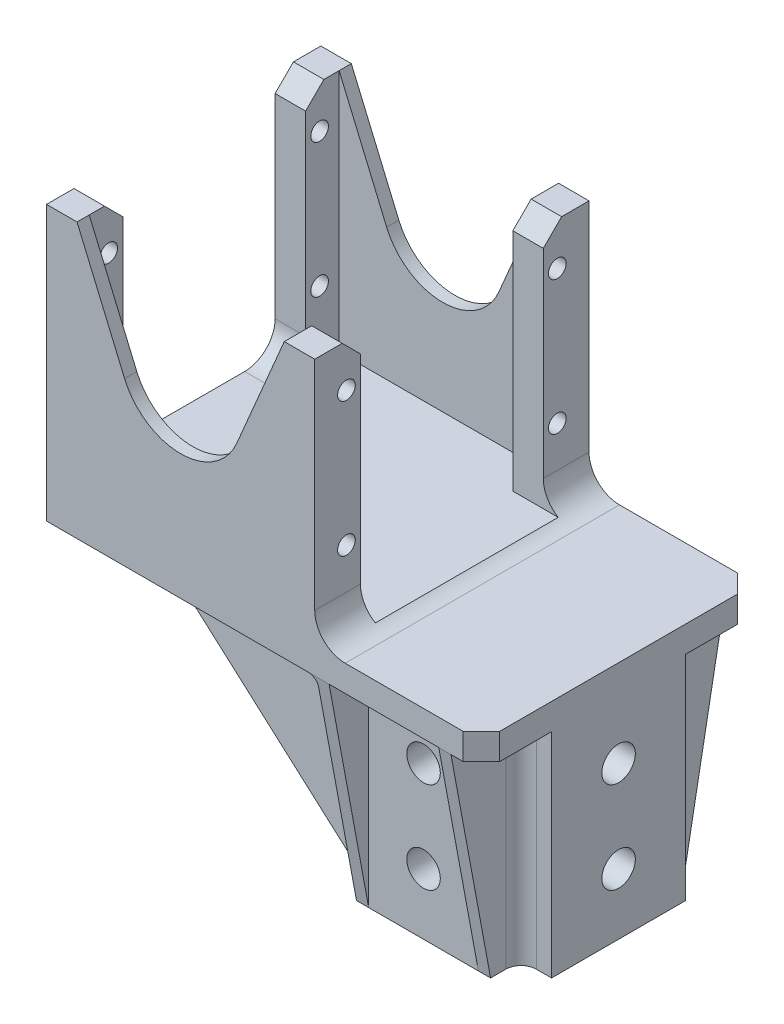
SolidWorks part; units mm, degrees
material "PLA"
ref_plane "Front Plane" through (0, 0, 0) normal (0, 0, 1) x (1, 0, 0)
ref_plane "Top Plane" through (0, 0, 0) normal (0, 1, 0) x (1, 0, 0)
ref_plane "Right Plane" through (0, 0, 0) normal (1, 0, 0) x (0, 0, -1)
sketch "Sketch2" plane through (0, 0, 0) normal (0, 0, 1) x (1, 0, 0)
  line L0 (12.8375, 22.5) -> (17.8375, 22.5) construction
  line L1 (-53.5125, 22.5) -> (17.8375, 22.5) construction
  line L2 (-17.8375, 22.5) -> (-17.8375, -22.5) construction
  line L3 (-53.5125, -22.5) -> (17.8375, -22.5)
  line L4 (17.8375, 22.5) -> (17.8375, -22.5) construction
  line L5 (-17.8375, 22.5) -> (17.8375, -22.5) construction
  line L6 (-17.8375, -22.5) -> (17.8375, 22.5) construction
  line L7 (-48.5125, 22.5) -> (12.8375, 22.5) construction
  line L8 (-17.8375, 22.5) -> (-17.8375, -17.5) construction
  line L9 (-48.5125, -17.5) -> (12.8375, -17.5) construction
  line L10 (12.8375, 22.5) -> (12.8375, -17.5) construction
  line L11 (-17.8375, 22.5) -> (12.8375, -17.5) construction
  line L12 (-17.8375, -17.5) -> (12.8375, 22.5) construction
  line L14 (-17.8375, -17.5) -> (-48.5125, 22.5) construction
  line L15 (-17.8375, 22.5) -> (-48.5125, -17.5) construction
  line L16 (-17.8375, -22.5) -> (-53.5125, 22.5) construction
  line L17 (-17.8375, 22.5) -> (-53.5125, -22.5) construction
  line L18 (-48.5125, 22.5) -> (-48.5125, -17.5)
  line L19 (-53.5125, 22.5) -> (-53.5125, -22.5)
  line L20 (-48.5125, 22.5) -> (-53.5125, 22.5)
  line L22 (-9.5125, -17.5) -> (-9.5125, 22.5)
  line L23 (-9.5125, 22.5) -> (-14.5125, 22.5)
  line L24 (-14.5125, 22.5) -> (-14.5125, -17.5)
  line L26 (17.8375, -17.5) -> (17.8375, -22.5)
  line L27 (-48.5125, -17.5) -> (-14.5125, -17.5)
  line L28 (-9.5125, -17.5) -> (17.8375, -17.5)
  point P4 (0, 0)
  point P8 (-2.5, 2.5)
  point P14 (-33.175, 2.5)
  point P15 (-35.675, 0)
  dimension "D1" = 5
  dimension "D2" = 40
  dimension "D3" = 27.35
  dimension "D4" = 5
  dimension "D5" = 34
  dimension "D6" = 5
extrude "Boss-Extrude1" add sketch "Sketch2" along normal blind 45
sketch "Sketch3" plane through (-53.5125, 0, 0) normal (1, 0, 0) x (0, 0, -1)
  line L0 (-5.2, 22.5) -> (-5.2, -22.5) construction
  line L2 (-39.8, 22.5) -> (-39.8, -22.5) construction
  line L4 (-37.5, 22.5) -> (-7.5, 22.5)
  line L5 (-37.5, 22.5) -> (-37.5, -17.5)
  line L6 (-37.5, -17.5) -> (-7.5, -17.5)
  line L7 (-7.5, 22.5) -> (-7.5, -17.5)
  line L8 (-37.5, 22.5) -> (-7.5, -17.5) construction
  line L9 (-37.5, -17.5) -> (-7.5, 22.5) construction
  line L10 (-45, 22.5) -> (0, 22.5) construction
  line L11 (-39.8, 15.5) -> (-5.2, 15.5) construction
  line L12 (-39.8, -6.5) -> (-5.2, -6.5) construction
  line L13 (-45, -22.5) -> (0, -22.5) construction
  circle A2 centre (-5.2, 15.5) radius 1.25 construction
  circle A3 centre (-5.2, -6.5) radius 1.25 construction
  circle A4 centre (-39.8, 15.5) radius 1.25 construction
  circle A5 centre (-39.8, -6.5) radius 1.25 construction
  point P10 (-22.5, 2.5)
  dimension "D4" = 2.3
  dimension "D7" = 2.5
  dimension "D5" = 2.5
  dimension "D6" = 2.5
  dimension "D9" = 2.5
  dimension "D8" = 22
  dimension "D1" = 30
  dimension "D2" = 5
  dimension "D3" = 2.3
  dimension "D10" = 11
extrude "Cut-Extrude1" cut sketch "Sketch3" along normal through all
sketch "Sketch4" plane through (0, -22.5, 0) normal (0, -1, 0) x (1, 0, 0)
  line L0 (-53.5125, 22.5) -> (17.8375, 22.5) construction
  line L1 (17.8375, 45) -> (17.8375, 0) construction
  line L3 (-53.5125, 45) -> (-53.5125, 0) construction
  line L10 (-8.4125, 32.75) -> (12.0875, 32.75)
  line L11 (-8.4125, 32.75) -> (-8.4125, 12.25)
  line L12 (-8.4125, 12.25) -> (12.0875, 12.25)
  line L13 (12.0875, 32.75) -> (12.0875, 12.25)
  line L14 (-8.4125, 32.75) -> (12.0875, 12.25) construction
  line L15 (-8.4125, 12.25) -> (12.0875, 32.75) construction
  line L16 (-14.1625, 38.5) -> (17.8375, 38.5)
  line L17 (-14.1625, 38.5) -> (-14.1625, 6.5)
  line L18 (-14.1625, 6.5) -> (17.8375, 6.5)
  line L19 (17.8375, 38.5) -> (17.8375, 6.5)
  line L20 (-14.1625, 38.5) -> (17.8375, 6.5) construction
  line L21 (-14.1625, 6.5) -> (17.8375, 38.5) construction
  circle A0 centre (1.8375, 22.5) radius 2.5
  point P18 (1.8375, 22.5)
  point P23 (1.8375, 22.5)
  dimension "D1" = 5
  dimension "D2" = 20.5
  dimension "D3" = 20.5
  dimension "D4" = 32
extrude "Boss-Extrude2" add sketch "Sketch4" along normal blind 35 contours L19 L16 L17 L18 L10 L13 L12 L11 region at (1.8375, -22.5, 38.0475)
sketch "Sketch5" plane through (0, 0, 38.5) normal (0, 0, 1) x (1, 0, 0)
  line L0 (1.8375, -22.5) -> (1.8375, -57.5) construction
  line L3 (-14.1625, -22.5) -> (17.8375, -22.5) construction
  line L4 (-14.1625, -57.5) -> (17.8375, -57.5) construction
  circle A0 centre (1.8375, -32.5) radius 2.5 construction
  circle A1 centre (1.8375, -47.5) radius 2.5 construction
  dimension "D2" = 5
  dimension "D3" = 5
  dimension "D4" = 10
  dimension "D1" = 15
sketch "Sketch6" plane through (0, -57.5, 0) normal (0, -1, 0) x (-1, 0, 0)
  line L1 (14.1625, -38.5) -> (9.1625, -38.5)
  line L2 (14.1625, -38.5) -> (14.1625, -33.5)
  line L3 (14.1625, -33.5) -> (9.1625, -33.5)
  line L4 (9.1625, -38.5) -> (9.1625, -33.5)
  line L5 (14.1625, -38.5) -> (9.1625, -33.5) construction
  line L6 (14.1625, -33.5) -> (9.1625, -38.5) construction
  line L7 (-17.8375, -38.5) -> (-12.8375, -38.5)
  line L8 (-17.8375, -38.5) -> (-17.8375, -33.5)
  line L9 (-17.8375, -33.5) -> (-12.8375, -33.5)
  line L10 (-12.8375, -38.5) -> (-12.8375, -33.5)
  line L11 (-17.8375, -38.5) -> (-12.8375, -33.5) construction
  line L12 (-17.8375, -33.5) -> (-12.8375, -38.5) construction
  line L13 (-17.8375, -6.5) -> (-12.8375, -6.5)
  line L14 (-17.8375, -6.5) -> (-17.8375, -11.5)
  line L15 (-17.8375, -11.5) -> (-12.8375, -11.5)
  line L16 (-12.8375, -6.5) -> (-12.8375, -11.5)
  line L17 (-17.8375, -6.5) -> (-12.8375, -11.5) construction
  line L18 (-17.8375, -11.5) -> (-12.8375, -6.5) construction
  line L19 (14.1625, -6.5) -> (9.1625, -6.5)
  line L20 (14.1625, -6.5) -> (14.1625, -11.5)
  line L21 (14.1625, -11.5) -> (9.1625, -11.5)
  line L22 (9.1625, -6.5) -> (9.1625, -11.5)
  line L23 (14.1625, -6.5) -> (9.1625, -11.5) construction
  line L24 (14.1625, -11.5) -> (9.1625, -6.5) construction
  point P4 (11.6625, -36)
  point P11 (-15.3375, -36)
  point P18 (-15.3375, -9)
  point P25 (11.6625, -9)
  dimension "D1" = 5
  dimension "D2" = 5
  dimension "D3" = 5
  dimension "D4" = 5
extrude "Cut-Extrude4" cut sketch "Sketch6" against normal up to surface (35 mm away) up to face at (-8, -22.5, 22.5)
sketch "Sketch9" plane through (0, 0, 33.5) normal (0, 0, 1) x (1, 0, 0)
  line L0 (-14.1625, -57.5) -> (-53.5125, -22.5)
  line L1 (-53.5125, -22.5) -> (17.8375, -22.5) construction
  line L2 (-53.5125, -22.5) -> (17.8375, -22.5) construction
rib "Rib1" sketch "Sketch9" sketch "Sketch9" thickness 2 extrusion direction parallel to sketch draft on no parameters "D1"=2
pattern_linear "LPattern1" count 2 spacing 20 along (0, 0, -1) of "Rib1"
sketch "Sketch14" plane through (12.8375, 0, 0) normal (1, 0, 0) x (0, 0, -1)
  line L0 (-6.5, -57.5) -> (0, -22.5)
rib "Rib6" sketch "Sketch14" sketch "Sketch14" thickness 2 extrusion direction parallel to sketch draft on no parameters "D1"=2
sketch "Sketch15" plane through (-9.1625, 0, 0) normal (-1, 0, 0) x (0, 0, 1)
  line L0 (6.5, -57.5) -> (0, -22.5)
rib "Rib7" sketch "Sketch15" sketch "Sketch15" thickness 2 extrusion direction parallel to sketch draft on no parameters "D1"=2
fillet "Fillet2" radius 5 3 edges at (-14.1625, -22.5, 22.5) (1.8375, -22.5, 6.5) (1.8375, -22.5, 38.5)
fillet "Fillet3" radius 5 2 edges at (-9.5125, -17.5, 3.75) (-9.5125, -17.5, 41.25)
sketch "Sketch17" plane through (0, 0, 45) normal (0, 0, 1) x (1, 0, 0)
  line L0 (-48.5125, 22.5) -> (-31.5125, -17.5)
  line L1 (-14.5125, -17.5) -> (-48.5125, -17.5) construction
rib "Rib10" sketch "Sketch17" sketch "Sketch17" thickness 2 extrusion direction parallel to sketch draft on no parameters "D1"=2
sketch "Sketch18" plane through (0, 0, 45) normal (0, 0, 1) x (1, 0, 0)
  line L0 (-31.5125, -17.5) -> (-14.5125, 22.5)
rib "Rib11" sketch "Sketch18" sketch "Sketch18" thickness 2 extrusion direction parallel to sketch draft on no parameters "D1"=2
fillet "Fillet4" radius 10 1 edges at (-31.5125, -17.5, 44)
pattern_linear "LPattern2" count 2 spacing 43 along (0, 0, -1) of "Fillet4", "Rib11", "Rib10"
hole_wizard "M5 Clearance Hole2" positions "Sketch20" profile "Sketch22" hole size "M5" standard "ISO"
sketch "Sketch20" plane through (0, 0, 38.5) normal (0, 0, 1) x (1, 0, 0)
  point P0 (1.8375, -32.5)
  point P3 (1.8375, -47.5)
sketch "Sketch22" plane through (1.8375, -32.5, 38.5) normal (1, 0, 0) x (0, -1, 0)
  line L0 (0, 0) -> (0, 7.6524)
  line L1 (0, 7.6524) -> (2.75, 6)
  line L2 (2.75, 6) -> (2.75, 0)
  line L5 (2.75, 0) -> (0, 0)
  line L10 (0, 7.6524) -> (-2.75, 6) construction
  line L11 (0, -6.35) -> (0, 107.95) construction
  dimension "Hole Dia." = 5.5
  dimension "Hole Depth" = 6
  dimension "Drill Angle" = 118
hole_wizard "M2.5 Clearance Hole1" positions "Sketch23" profile "Sketch24" hole size "M2.5" standard "ISO" end condition through all
sketch "Sketch23" plane through (-53.5125, 0, 0) normal (-1, 0, 0) x (0, 0, 1)
  point P0 (5.2, 15.5)
  point P3 (39.8, 15.5)
  point P6 (39.8, -6.5)
  point P9 (5.2, -6.5)
sketch "Sketch24" plane through (-53.5125, 15.5, 5.2) normal (0, 1, 0) x (0, 0, 1)
  line L0 (0, 0) -> (0, 71.35)
  line L1 (0, 71.35) -> (1.45, 71.35)
  line L2 (1.45, 71.35) -> (1.45, 0)
  line L5 (1.45, 0) -> (0, 0)
  line L11 (0, -6.35) -> (0, 107.95) construction
  dimension "Thru Hole Dia." = 2.9
  dimension "Thru Hole Depth" = 71.35
fillet "Fillet5" radius 2.5 4 edges at (-9.1625, -40, 11.5) (-9.1625, -40, 33.5) (12.8375, -40, 33.5) (12.8375, -40, 11.5)
extrude "Boss-Extrude4" add sketch "Sketch4<4>" along normal blind 8 contours A0 region at (1.8375, -22.5, 22.5)
sketch "Sketch4<4>" plane through (0, -22.5, 0) normal (0, -1, 0) x (1, 0, 0) same geometry as "Sketch4"
pattern_circular "CirPattern1" count 4 every 90 about axis through (1.8375, -30.5, 22.5) along (0, -1, 0) of "M5 Clearance Hole2"
ref_axis "Axis2" through (1.8375, -30.5, 22.5) along (0, 1, 0)
ref_plane "Plane1" through (0, 0, 22.5) normal (0, 0, 1) x (1, 0, 0)
mirror "Mirror1" about plane through (0, 0, 22.5) normal (0, 0, 1) of "Rib6", "Rib7"
chamfer "Chamfer1" distance 3 angle 45 6 edges at (17.8375, -20, 0) (17.8375, -20, 45) (-51.0125, 22.5, 37.5) (-51.0125, 22.5, 7.5) (-12.0125, 22.5, 7.5) (-12.0125, 22.5, 37.5)
fillet "Fillet6" radius 5 2 edges at (-51.0125, -17.5, 37.5) (-51.0125, -17.5, 7.5)
fillet "Fillet7" radius 1.5 12 edges at (-9.1625, -22.5, 4.5) (-9.8947, -22.5, 10.7678) (-14.1625, -42.5, 13.5) (-15.627, -23.9645, 13.5) (-14.1625, -42.5, 31.5) (-15.627, -23.9645, 31.5) (-9.1625, -22.5, 40.5) (-9.8947, -22.5, 34.2322) (-32.5875, -22.5, 11.5) (-36.3375, -22.5, 13.5) (-36.3375, -22.5, 31.5) (-32.5875, -22.5, 33.5)
sketch "Sketch27" plane through (0, 0, 45) normal (0, 0, 1) x (1, 0, 0)
  line L0 (17.8375, -17.5) -> (17.8375, -22.5) construction
  line L1 (-9.5125, -12.5) -> (17.8375, -12.5)
  line L2 (-9.5125, -12.5) -> (-9.5125, -18.2)
  line L3 (-9.5125, -18.2) -> (17.8375, -18.2)
  line L4 (17.8375, -12.5) -> (17.8375, -18.2)
  line L5 (10.8375, -22.5) -> (12.8375, -22.5) construction
  dimension "D1" = 4.3
extrude "Cut-Extrude6" cut sketch "Sketch27" against normal through all
sketch "Sketch28" plane through (0, 0, 45) normal (0, 0, 1) x (1, 0, 0)
  line L1 (-9.5125, -18.2) -> (-4.5125, -18.2)
  line L2 (-9.5125, -18.2) -> (-9.5125, -13.2)
  line L3 (-9.5125, -13.2) -> (-4.5125, -13.2)
  line L4 (-4.5125, -18.2) -> (-4.5125, -13.2)
  dimension "D1" = 5
  dimension "D2" = 5
fillet "Fillet8" radius 5 1 edges at (-9.5125, -18.2, 22.5)
